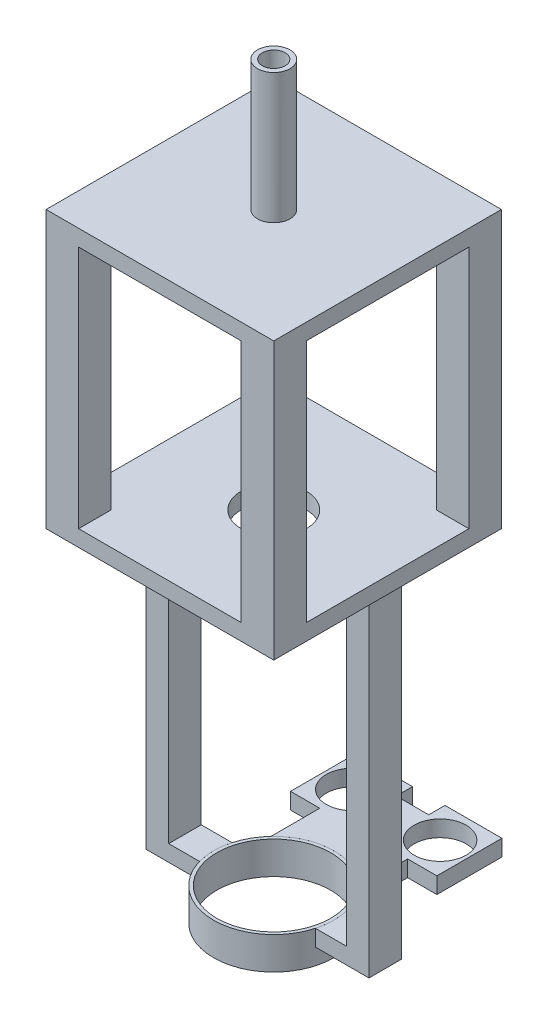
SolidWorks part; units mm, degrees
ref_plane "Front Plane" through (0, 0, 0) normal (0, 0, 1) x (1, 0, 0)
ref_plane "Top Plane" through (0, 0, 0) normal (0, 1, 0) x (1, 0, 0)
ref_plane "Right Plane" through (0, 0, 0) normal (1, 0, 0) x (0, 0, -1)
sketch "Sketch2" plane through (0, 0, 0) normal (0, 1, 0) x (1, 0, 0)
  line L0 (0, 17.5) -> (0, -17.5) construction
  line L1 (-17.5, 0) -> (17.5, 0) construction
  line L2 (-17.5, 0) -> (-17.5, 5) construction
  line L3 (-16.7705, 5) -> (-34.2705, 5)
  line L4 (-34.2705, 5) -> (-34.2705, -5)
  line L5 (-16.7705, -5) -> (-34.2705, -5)
  line L6 (16.7705, -5) -> (34.2705, -5)
  line L7 (34.2705, 5) -> (34.2705, -5)
  line L8 (16.7705, 5) -> (34.2705, 5)
  line L9 (0, 27.6491) -> (22.5, 27.6491)
  line L10 (22.5, 27.6491) -> (22.5, 47.6491)
  line L11 (22.5, 47.6491) -> (5, 47.6491)
  line L12 (-22.5, 47.6491) -> (-22.5, 27.6491)
  line L13 (-22.5, 27.6491) -> (0, 27.6491)
  line L14 (22.5, 37.6491) -> (21.5, 37.6491) construction
  line L20 (-5, 47.6491) -> (-22.5, 47.6491)
  line L21 (0, 42.6491) -> (0, 27.6491) construction
  line L22 (-5, 47.6491) -> (-5, 42.6491)
  line L23 (-5, 42.6491) -> (5, 42.6491)
  line L24 (5, 42.6491) -> (5, 47.6491)
  line L25 (13.5, 45.6491) -> (13.5, 47.6491) construction
  line L26 (13.5, 29.6491) -> (13.5, 27.6491) construction
  line L27 (-13.5, 37.6491) -> (13.5, 37.6491) construction
  line L28 (-13.5, 12.6491) -> (-13.5, 27.6491)
  line L29 (13.5, 27.6491) -> (13.5, 12.6491)
  line L30 (-18.5, 0) -> (-27.3, 0) construction
  line L31 (-27.3, 5) -> (-27.3, -5)
  line L32 (27.3, 5) -> (27.3, -5)
  circle A0 centre (0, 0) radius 17.5
  circle A1 centre (0, 0) radius 18.5
  circle A2 centre (13.5, 37.6491) radius 8
  circle A3 centre (-13.5, 37.6491) radius 8
  point P13 (-34.2705, 0)
  dimension "D1" = 35
  dimension "D2" = 17.5
  dimension "D4" = 37
  dimension "D8" = 1
  dimension "D9" = 16
  dimension "D3" = 5
  dimension "D5" = 5
  dimension "D6" = 20
  dimension "D7" = 45
  dimension "D10" = 17.5
  dimension "D11" = 8.8
  dimension "D12" = 27
  dimension "D13" = 15
extrude "Connector sleeve" add sketch "Sketch2" along normal blind 5 and the other way blind 5 contours L5 A1 L6 A0 | L8 A1 L3 A0 | L6 A1 L8 A0 | L3 A1 L5 A0 region at (-15.7843, 0, -8.897) region at (-17.7631, 0, 0) region at (-17.291, 0, 5.381) region at (17.7631, 0, 0)
ref_plane "Plane2" through (0, 30, 0) normal (0, 1, 0) x (1, 0, 0)
extrude "Sensor holder" add sketch "Sketch2<10>" along normal blind 5 separate body contours L24 L23 L22 L20 L12 L13 L9 L10 L11 A2 A3 | A1 L29 L9 L13 L28 | A1 L3 L31 L5 | L31 L3 L4 L5 | A1 L6 L32 L8 | L8 L32 L6 L7 region at (-30.7853, 0, 0) region at (-22.7838, 0, 0) region at (0, 0, -22.0403) region at (0, 0, -36.8118) region at (22.7838, 0, 0) region at (30.7853, 0, 0)
sketch "Sketch2<10>" plane through (0, 0, 0) normal (0, 1, 0) x (1, 0, 0) same geometry as "Sketch2"
extrude "Boss-Extrude1" add sketch "Sketch2<18>" along normal blind 100 contours L31 L3 L4 L5 | L8 L32 L6 L7 region at (-30.7853, 0, 0) region at (30.7853, 0, 0)
sketch "Sketch2<18>" plane through (0, 0, 0) normal (0, 1, 0) x (1, 0, 0) same geometry as "Sketch2"
sketch "Sketch4" plane through (0, 100, 0) normal (0, 1, 0) x (1, 0, 0)
  line L1 (-35, -35) -> (35, -35)
  line L2 (-35, -35) -> (-35, 35)
  line L3 (-35, 35) -> (35, 35)
  line L4 (35, -35) -> (35, 35)
  line L5 (-35, -35) -> (35, 35) construction
  line L6 (-35, 35) -> (35, -35) construction
  circle A0 centre (0, 0) radius 10
  point P0 (0, 0)
  dimension "D2" = 20
  dimension "D1" = 70
extrude "Motor enclosure" add sketch "Sketch4" along normal blind 5
sketch "Sketch6" plane through (0, 105, 0) normal (0, 1, 0) x (1, 0, 0)
  line L0 (-35, 35) -> (-25, 35)
  line L1 (35, 35) -> (-35, 35) construction
  line L2 (-25, 35) -> (-25, 25)
  line L3 (-25, 25) -> (-35, 25)
  line L4 (-35, 35) -> (-35, -35) construction
  line L5 (-35, 25) -> (-35, 35)
  line L6 (0, 35) -> (0, -35) construction
  line L7 (-35, -35) -> (35, -35) construction
  line L8 (-35, 0) -> (35, 0) construction
  line L9 (35, -35) -> (35, 35) construction
  line L10 (25, 25) -> (35, 25)
  line L11 (35, 25) -> (35, 35)
  line L12 (35, 35) -> (25, 35)
  line L13 (25, 35) -> (25, 25)
  line L14 (25, -25) -> (35, -25)
  line L15 (35, -25) -> (35, -35)
  line L16 (35, -35) -> (25, -35)
  line L17 (25, -35) -> (25, -25)
  line L18 (-25, -25) -> (-35, -25)
  line L19 (-25, -35) -> (-25, -25)
  line L20 (-35, -25) -> (-35, -35)
  line L21 (-35, -35) -> (-25, -35)
  dimension "D2" = 10
extrude "Motor enclosure 2" add sketch "Sketch6" along normal blind 75
sketch "Sketch7" plane through (0, 180, 0) normal (0, 1, 0) x (1, 0, 0)
  line L0 (-35, 35) -> (35, 35)
  line L1 (35, 35) -> (35, -35)
  line L2 (35, -35) -> (-35, -35)
  line L3 (-35, -25) -> (-35, -35) construction
  line L4 (-35, -35) -> (-35, 35)
extrude "Motor enclosure 3" add sketch "Sketch7" along normal blind 5 contours L1 L2 L4 L0
sketch "Sketch8" plane through (0, 185, 0) normal (0, 1, 0) x (1, 0, 0)
  circle A0 centre (0, 0) radius 5
  point P0 (0, 0)
  dimension "D1" = 10
extrude "Boss-Extrude5" add sketch "Sketch8" along normal blind 40
sketch "Sketch26" plane through (0, 225, 0) normal (0, 1, 0) x (1, 0, 0)
  circle A0 centre (0, 0) radius 3.5
  dimension "D1" = 7
extrude "Cut-Extrude1" cut sketch "Sketch26" against normal up to next (45 mm away)
